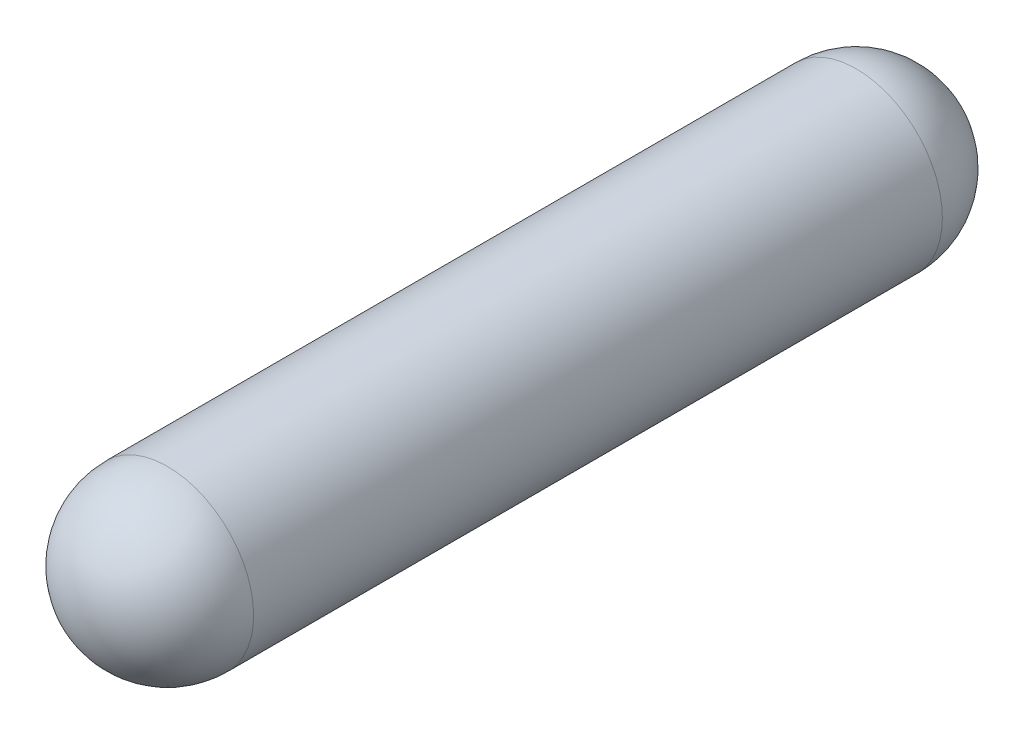
SolidWorks part; units mm, degrees
material "Chrome Stainless Steel"
ref_plane "Front Plane" through (0, 0, 0) normal (0, 0, 1) x (1, 0, 0)
ref_plane "Top Plane" through (0, 0, 0) normal (0, 1, 0) x (1, 0, 0)
ref_plane "Right Plane" through (0, 0, 0) normal (1, 0, 0) x (0, 0, -1)
sketch "BaseS" plane through (0, 0, 0) normal (0, 0, 1) x (1, 0, 0)
  circle A0 centre (0, 0) radius 0.3
  dimension "Dia" = 0.6
extrude "Base" add sketch "BaseS" against normal mid plane 2.4
dome "FrontDome" faces to dome 1 distance 0.3 reverse direction no elliptical dome no face at (0.3, 0, 1.2) parameters "Radius"=0.3
dome "RearDome" faces to dome 1 distance 0.3 reverse direction no elliptical dome no face at (0.3, 0, -1.2) parameters "Radius"=0.3
